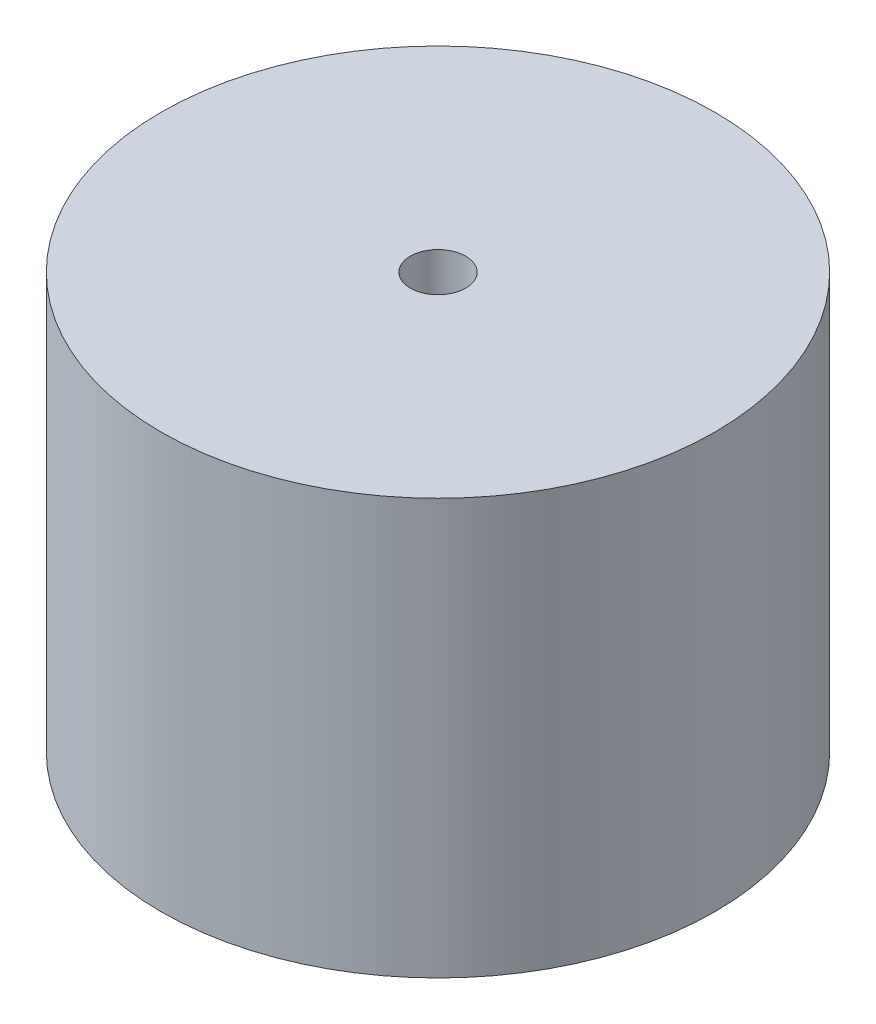
SolidWorks part; units mm, degrees
ref_plane "前视基准面" through (0, 0, 0) normal (0, 0, 1) x (1, 0, 0)
ref_plane "上视基准面" through (0, 0, 0) normal (0, 1, 0) x (1, 0, 0)
ref_plane "右视基准面" through (0, 0, 0) normal (1, 0, 0) x (0, 0, -1)
other "Configuration Table"
sketch "草图1" plane through (0, 0, 0) normal (0, 1, 0) x (1, 0, 0)
  line L0 (-5, 0) -> (-2.75, 0)
  circle A0 centre (0, 0) radius 2.75
  circle A1 centre (0, 0) radius 5
  circle A2 centre (0, 0) radius 0.5
  circle A3 centre (-3.875, 0) radius 0.35
  circle A4 centre (-3.875, 0) radius 0.6
  dimension "D1" = 10
  dimension "D2" = 5.5
  dimension "D3" = 1
  dimension "D4" = 0.7
  dimension "D5" = 1.2
extrude "凸台-拉伸1" add sketch "草图1" along normal blind 7.5 contours A1
extrude "切除-拉伸1" cut sketch "草图1<5>" along normal blind 6.5 contours A0
sketch "草图1<5>" plane through (0, 0, 0) normal (0, 1, 0) x (1, 0, 0) same geometry as "草图1"
extrude "切除-拉伸2" cut sketch "草图1<6>" along normal through all contours A2
sketch "草图1<6>" plane through (0, 0, 0) normal (0, 1, 0) x (1, 0, 0) same geometry as "草图1"
extrude "切除-拉伸3" cut sketch "草图1<7>" along normal blind 2 contours A3
sketch "草图1<7>" plane through (0, 0, 0) normal (0, 1, 0) x (1, 0, 0) same geometry as "草图1"
pattern_circular "阵列(圆周)1" count 4 over 360 about axis through (0, 7.5, 0) along (0, -1, 0) of "切除-拉伸3" reverse direction yes
